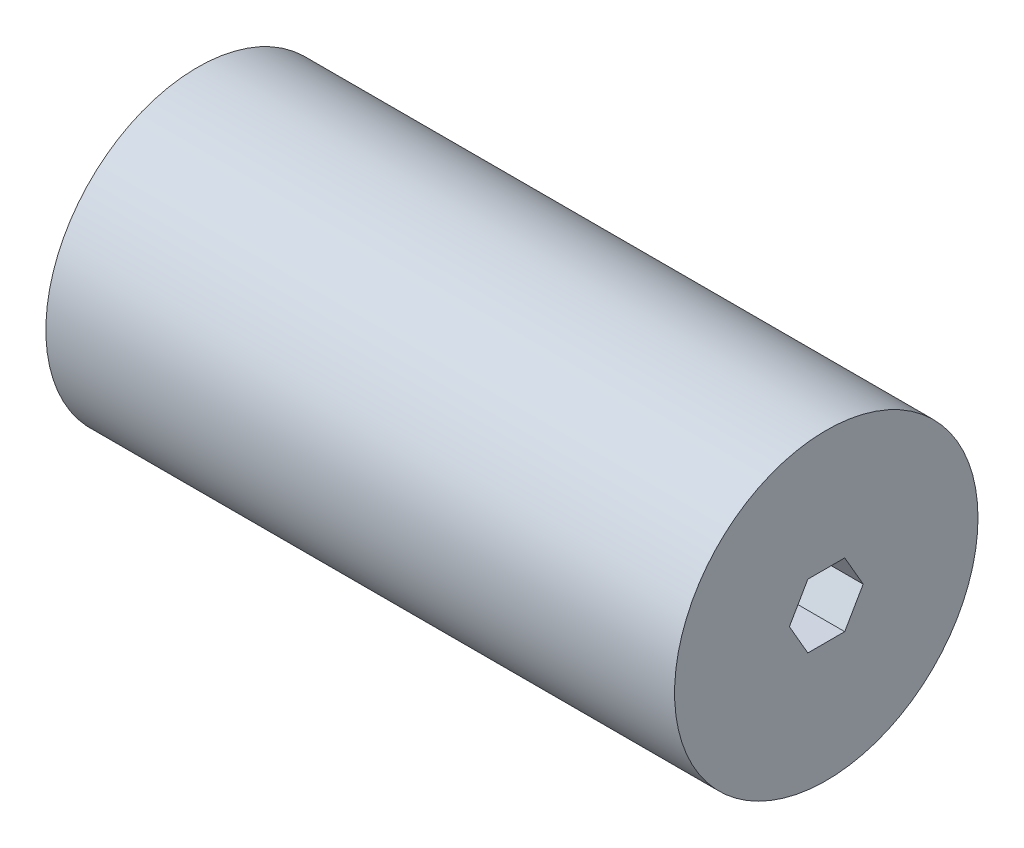
SolidWorks part; units mm, degrees
ref_plane "Front Plane" through (0, 0, 0) normal (0, 0, 1) x (1, 0, 0)
ref_plane "Top Plane" through (0, 0, 0) normal (0, 1, 0) x (1, 0, 0)
ref_plane "Right Plane" through (0, 0, 0) normal (1, 0, 0) x (0, 0, -1)
sketch "Sketch1" plane through (0, 0, 0) normal (1, 0, 0) x (0, 0, -1)
  line L1 (7.3323, 0) -> (3.6662, 6.35)
  line L2 (3.6662, 6.35) -> (-3.6662, 6.35)
  line L3 (-3.6662, 6.35) -> (-7.3323, 0)
  line L4 (-7.3323, 0) -> (-3.6662, -6.35)
  line L5 (-3.6662, -6.35) -> (3.6662, -6.35)
  line L6 (3.6662, -6.35) -> (7.3323, 0)
  circle A0 centre (0, 0) radius 30.1625
  circle A1 centre (0, 0) radius 6.35 construction
  dimension "D1" = 12.7
  dimension "D2" = 60.325
extrude "Boss-Extrude1" add sketch "Sketch1" along normal mid plane 125
ref_axis "Axis1" through (-59.0275, 0, 0) along (1, 0, 0)
